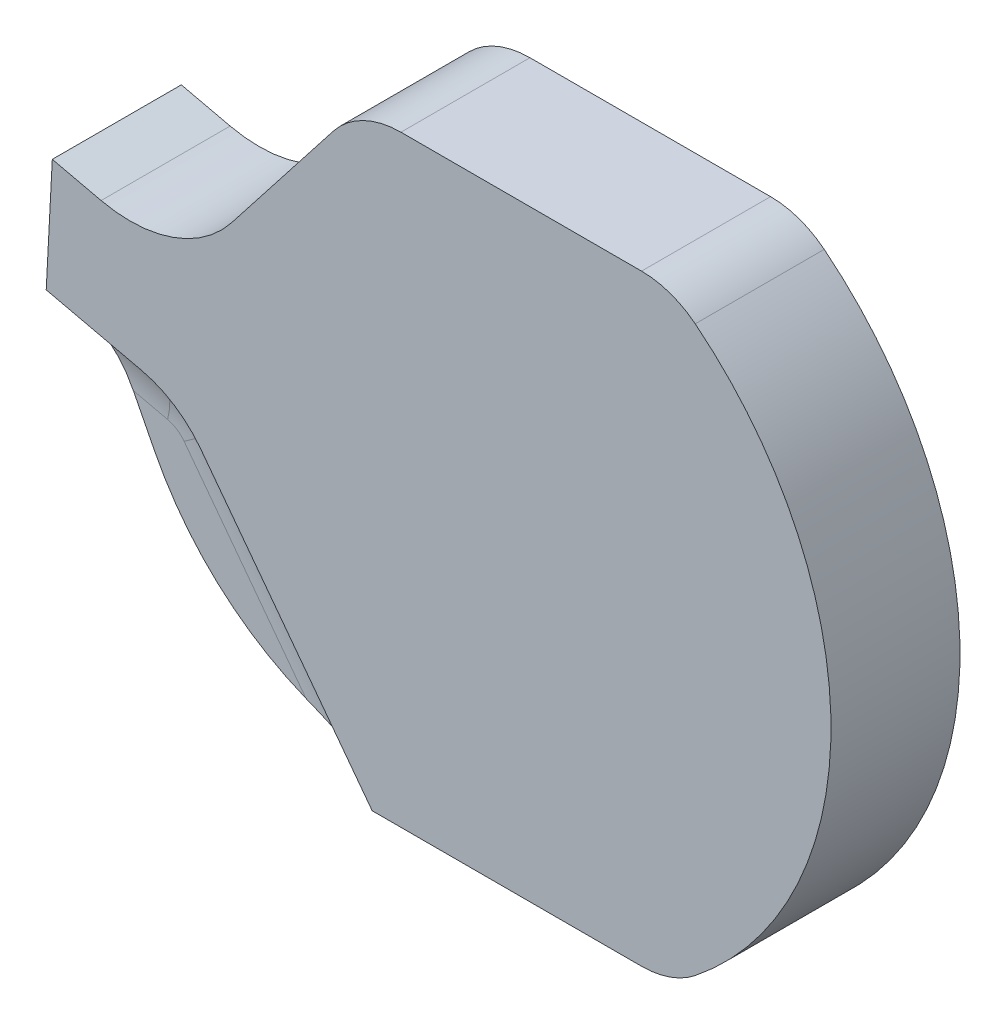
SolidWorks part; units mm, degrees
material "AISI 4340 Aço, normalizado"
ref_plane "Plano frontal" through (0, 0, 0) normal (0, 0, 1) x (1, 0, 0)
ref_plane "Plano superior" through (0, 0, 0) normal (0, 1, 0) x (1, 0, 0)
ref_plane "Plano direito" through (0, 0, 0) normal (1, 0, 0) x (0, 0, -1)
other "Center of Mass"
sketch "Sketch2" plane through (0, 0, 0) normal (0, 0, 1) x (1, 0, 0)
  line L0 (0, 0) -> (-50, 0) construction
  line L1 (-42.8615, 10.6893) -> (-48.5386, 12)
  line L2 (0, 0) -> (-49.5134, 6.9587) construction
  line L5 (-8, 35) -> (19.975, 35)
  line L6 (0, 0) -> (0, 41.2714) construction
  line L8 (-15.8801, 31.1566) -> (-27.6671, 16.07)
  line L14 (-8, -35) -> (19.975, -35)
  line L18 (-8, -35) -> (-11.3418, -35)
  line L19 (-48.5386, 12) -> (-49.2461, -1.5)
  line L20 (-49.0491, 9.7888) -> (-47.3436, 17.1762) construction
  line L22 (-49.2461, -1.5) -> (-41.636, -16.4357)
  circle A0 centre (0, 0) radius 50 construction
  arc A1 (26.2172, 32.8125) -> (26.2172, -32.8125) centre (0, 0) cw
  arc A5 (19.975, 35) -> (26.2172, 32.8125) centre (19.975, 25) cw
  arc A6 (-8, 35) -> (-15.8801, 31.1566) centre (-8, 25) ccw
  arc A12 (19.975, -35) -> (26.2172, -32.8125) centre (19.975, -25) ccw
  arc A17 (-41.636, -16.4357) -> (-11.3418, -35) centre (-11.3418, -1) ccw
  arc A18 (-42.8615, 10.6893) -> (-27.6671, 16.07) centre (-39.4873, 25.3049) ccw
  point P29 (-50, 0)
  point P31 (23.2164, 35)
  point P32 (-12.8773, 35)
  dimension "D1" = 100
  dimension "D4" = 10
  dimension "D5" = 15
  dimension "D13" = 34
  dimension "D10" = 35
  dimension "D11" = 8
  dimension "D2" = 5
  dimension "D3" = 10
  dimension "D7" = 38
  dimension "D8" = 77
  dimension "D6" = 8
  dimension "D12" = 30
  dimension "D9" = 12
  dimension "D14" = 13.5
extrude "Boss-Extrude1" add sketch "Sketch2" along normal blind 15 contours L5 A5 A1 A12 L14 L18 A17 L22 L19 L1 A18 L8 A6
sketch "Esboço4" plane through (0, 0, 0) normal (0, 0, -1) x (-1, 0, 0)
  line L0 (49.2461, -1.5) -> (38.1752, -4.0559)
  line L1 (31.291, -8.5266) -> (11.3418, -35)
  line L2 (15.8801, 31.1566) -> (27.6671, 16.07) construction
  line L3 (42.8615, 10.6893) -> (48.5386, 12) construction
  line L4 (49.2461, -1.5) -> (41.636, -16.4357) construction
  line L5 (49.2461, -1.5) -> (41.636, -16.4357)
  arc A0 (11.3418, -35) -> (41.636, -16.4357) centre (11.3418, -1) ccw construction
  arc A1 (11.3418, -35) -> (41.636, -16.4357) centre (11.3418, -1) ccw
  arc A2 (38.1752, -4.0559) -> (31.291, -8.5266) centre (40.8746, -15.7484) ccw
  dimension "D2" = 12
  dimension "D1" = 105
extrude "Corte-extrusão1" cut sketch "Esboço4" against normal blind 5
extrude "Corte-extrusão2" cut sketch "Esboço4<2>" along normal blind 5 from surface starting at face at (-11.5758, 3.867, 15)
sketch "Esboço4<2>" plane through (0, 0, 0) normal (0, 0, -1) x (-1, 0, 0) same geometry as "Esboço4"
fillet "Filete1" radius 10 6 edges at (-21.3164, -21.7633, 10) (-43.7107, -2.778, 10) (-43.7107, -2.778, 5) (-21.3164, -21.7633, 5) (-34.3389, -5.6843, 10) (-34.3389, -5.6843, 5)
other "Ponto de referência do centro da massa1"
ref_plane "Plano2" through (0, -0.5025, 0) normal (0, 1, 0) x (1, 0, 0)
ref_plane "Plano3" through (1.5654, 0, 0) normal (1, 0, 0) x (0, 0, -1)
sketch "Esboço2" plane through (0, 0, 0) normal (0, 0, -1) x (-1, 0, 0)
  line L0 (8.25, -0.5025) -> (-8.25, -0.5025) construction
  line L1 (3.6299, 21.2463) -> (18.9508, 8.3905)
  line L2 (-10.4584, 20.0137) -> (-23.3142, 4.6928)
  line L3 (-22.0816, -9.3955) -> (-6.7607, -22.2512)
  line L4 (20.1834, -5.6978) -> (7.3276, -21.0187)
  line L5 (-4.0305, 27.6742) -> (0.8997, -28.6791) construction
  line L6 (-29.7421, -2.9676) -> (26.6112, 1.9627) construction
  line L7 (-1.5654, 8.25) -> (-1.5654, -8.25) construction
  line L10 (-2.503, -0.5025) -> (81.0211, -0.5025) construction
  circle A0 centre (-1.5654, -0.5025) radius 11
  arc A2 (3.6299, 21.2463) -> (-10.4584, 20.0137) centre (-2.798, 13.5858) ccw
  arc A3 (18.9508, 8.3905) -> (20.1834, -5.6978) centre (12.5229, 0.7301) cw
  arc A4 (-6.7607, -22.2512) -> (7.3276, -21.0187) centre (-0.3328, -14.5908) ccw
  arc A5 (-23.3142, 4.6928) -> (-22.0816, -9.3955) centre (-15.6537, -1.735) ccw
  dimension "D1" = 10
  dimension "D2" = 22
  dimension "D3" = 40
  dimension "D4" = 5
equation "\"escala\" = 1                        'projeto - escala geral"
equation "\"escala_disco-arma\"= \"escala\" * 1   'disco arma - escala geometria disco arma"
equation "\"rolamento_D-ext\"= 1                'rolamento arma - diametro externo"
equation "\"rolamento_d-int\"= 1                'rolamento arma - diametro interno"
equation "\"rolamento_b-esp\"= 1                'rolamento arma - espessura"
equation "\"arma_rebaixo-camisa_b\"= 1          'disco arma - profundidade rebaixo camisa"
equation "\"arma_dente_altura-centro\"= 20"
equation "\"arma-espessura\"= 15                'disco arma - espessura disco arma"
equation "\"D1@Boss-Extrude1\"=\"arma-espessura\""
equation "\"eixo_diam\"= 18                     'eixo arma - diametro"
equation "\"D2@Esboço2\" = \"eixo_diam\" + \"arma_eixo-furo_folga\""
equation "\"camisa_largura\"=40                 'camisa arma - tamanho do lado"
equation "\"D3@Esboço2\"=\"camisa_largura\""
equation "\"camisa_raio\"=10                    'camisa arma - raio canto interno"
equation "\"D1@Esboço2\"=\"camisa_raio\""
equation "\"arma_alivio_raio\"=12"
equation "\"D2@Esboço4\"= \"arma_alivio_raio\""
equation "\"arma_diam_max\"=100"
equation "\"D1@Sketch2\" = \"arma_diam_max\""
equation "\"arma_arestas_raio\"= 10"
equation "\"D4@Sketch2\" = \"arma_arestas_raio\""
equation "\"arma_altura_superior-centro\"=35"
equation "\"D10@Sketch2\" = \"arma_altura_superior-centro\""
equation "\"arma_dente_raio\"= 15"
equation "\"D5@Sketch2\" = \"arma_dente_raio\""
equation "\"arma_altura_dente-centro\"=12"
equation "\"D9@Sketch2\"=\"arma_altura_dente-centro\""
equation "\"arma_dente_altura\"=13.5"
equation "\"D14@Sketch2\"=\"arma_dente_altura\""
equation "\"arma_alivio-dente_raio\"=34"
equation "\"D13@Sketch2\"=\"arma_alivio-dente_raio\""
equation "\"arma_traseira_offset\"=8"
equation "\"D11@Sketch2\" = \"arma_traseira_offset\""
equation "\"arma_centralizacao_offset\"=8"
equation "\"D6@Sketch2\"=\"arma_centralizacao_offset\""
equation "\"arma_eixo-furo_folga\" = 4          'arma - folga entre furo arma e eixo"
